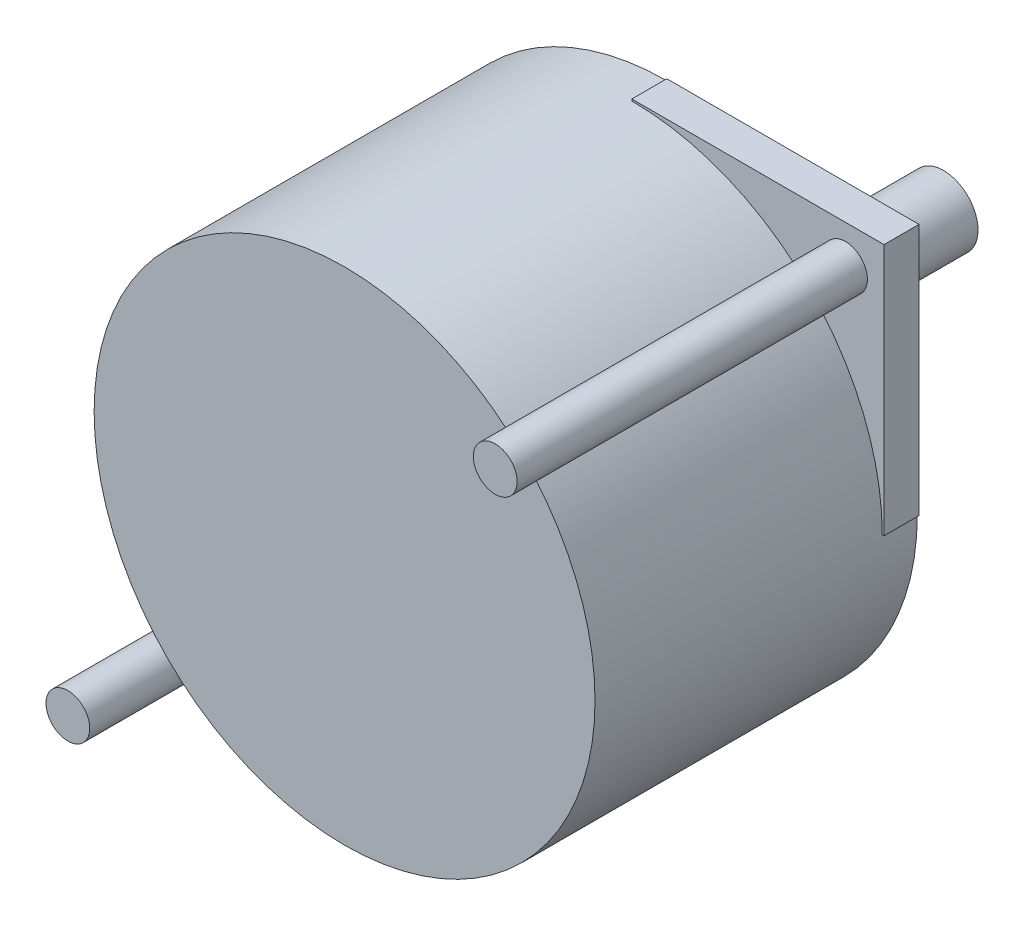
SolidWorks part; units mm, degrees
ref_plane "Front Plane" through (0, 0, 0) normal (0, 0, 1) x (1, 0, 0)
ref_plane "Top Plane" through (0, 0, 0) normal (0, 1, 0) x (1, 0, 0)
ref_plane "Right Plane" through (0, 0, 0) normal (1, 0, 0) x (0, 0, -1)
sketch "Sketch1" plane through (0, 0, 0) normal (0, 0, 1) x (1, 0, 0)
  line L1 (-0.6381, 0.9442) -> (35.9379, 0.9442)
  line L2 (-0.6381, 0.9442) -> (-0.6381, -35.6318)
  line L3 (-0.6381, -35.6318) -> (35.9379, -35.6318)
  line L4 (35.9379, 0.9442) -> (35.9379, -35.6318)
  dimension "D1" = 36.576
  dimension "D2" = 36.576
extrude "Boss-Extrude1" add sketch "Sketch1" along normal blind 2.54
sketch "Sketch2" plane through (0, 0, 2.54) normal (0, 0, 1) x (1, 0, 0)
  line L0 (35.9379, -17.3438) -> (-0.6381, -17.3438) construction
  line L1 (35.9379, -35.6318) -> (35.9379, 0.9442) construction
  line L2 (-0.6381, 0.9442) -> (-0.6381, -35.6318) construction
  line L3 (17.6499, 0.9442) -> (17.6499, -35.6318) construction
  line L6 (35.9379, 0.9442) -> (-0.6381, 0.9442) construction
  line L7 (-0.6381, -35.6318) -> (35.9379, -35.6318) construction
  line L8 (17.6499, -17.3438) -> (33.1439, -1.8498) construction
  line L9 (17.6499, -17.3438) -> (2.1559, -32.8378) construction
  circle A0 centre (33.1439, -1.8498) radius 1.5875
  circle A1 centre (2.1559, -32.8378) radius 1.5875
  dimension "D4" = 3.175
  dimension "D5" = 3.175
  dimension "D1" = 30.988
  dimension "D2" = 45
  dimension "D3" = 45
extrude "Boss-Extrude2" add sketch "Sketch2" along normal blind 25.4
sketch "Sketch3" plane through (0, 0, 2.54) normal (0, 0, 1) x (1, 0, 0)
  line L0 (-0.6381, 0.9442) -> (-0.6381, -17.3438)
  line L1 (-0.6381, 0.9442) -> (-0.6381, -35.6318) construction
  line L2 (-0.6381, -17.3438) -> (-0.5111, -17.3438)
  line L3 (-0.6381, 0.9442) -> (17.6499, 0.9442)
  line L4 (35.9379, 0.9442) -> (-0.6381, 0.9442) construction
  line L5 (17.6499, 0.9442) -> (17.6499, 0.8172)
  line L6 (35.9379, -35.6318) -> (17.6499, -35.6318)
  line L7 (-0.6381, -35.6318) -> (35.9379, -35.6318) construction
  line L8 (17.6499, -35.6318) -> (17.6499, -35.5048)
  line L9 (35.9379, -35.6318) -> (35.9379, -17.3438)
  line L10 (35.9379, -35.6318) -> (35.9379, 0.9442) construction
  line L11 (35.9379, -17.3438) -> (35.8109, -17.3438)
  arc A0 (17.6499, 0.8172) -> (-0.5111, -17.3438) centre (17.6499, -17.3438) ccw
  arc A1 (17.6499, -35.5048) -> (35.8109, -17.3438) centre (17.6499, -17.3438) ccw
  dimension "D1" = 36.322
extrude "Cut-Extrude4" cut sketch "Sketch3" against normal through all
sketch "Sketch4" plane through (0, 0, 0) normal (0, 0, -1) x (-1, 0, 0)
  line L0 (0.6381, -35.6318) -> (-35.9379, 0.9442) construction
  line L1 (-4.8081, -4.502) -> (-30.4917, -30.1856) construction
  arc A2 (0.5111, -17.3438) -> (-17.6499, 0.8172) centre (-17.6499, -17.3438) ccw construction
  arc A3 (-35.8109, -17.3438) -> (-17.6499, -35.5048) centre (-17.6499, -17.3438) ccw construction
  circle A4 centre (-17.6499, -17.3438) radius 8.001
  dimension "D1" = 16.002
extrude "Boss-Extrude3" add sketch "Sketch4" along normal blind 1.016
sketch "Sketch5" plane through (0, 0, -1.016) normal (0, 0, -1) x (-1, 0, 0)
  circle A0 centre (-17.6499, -17.3438) radius 2.4955
  dimension "D1" = 4.9911
extrude "Boss-Extrude4" add sketch "Sketch5" along normal blind 19.05
sketch "Sketch6" plane through (0, 0, 2.54) normal (0, 0, 1) x (1, 0, 0)
  line L0 (4.8081, -4.502) -> (30.4917, -30.1856) construction
  arc A0 (17.6499, 0.8172) -> (-0.5111, -17.3438) centre (17.6499, -17.3438) ccw construction
  arc A1 (17.6499, -35.5048) -> (35.8109, -17.3438) centre (17.6499, -17.3438) ccw construction
  circle A2 centre (17.6499, -17.3438) radius 18.161
  dimension "D1" = 36.322
extrude "Boss-Extrude5" add sketch "Sketch6" along normal blind 20.828
